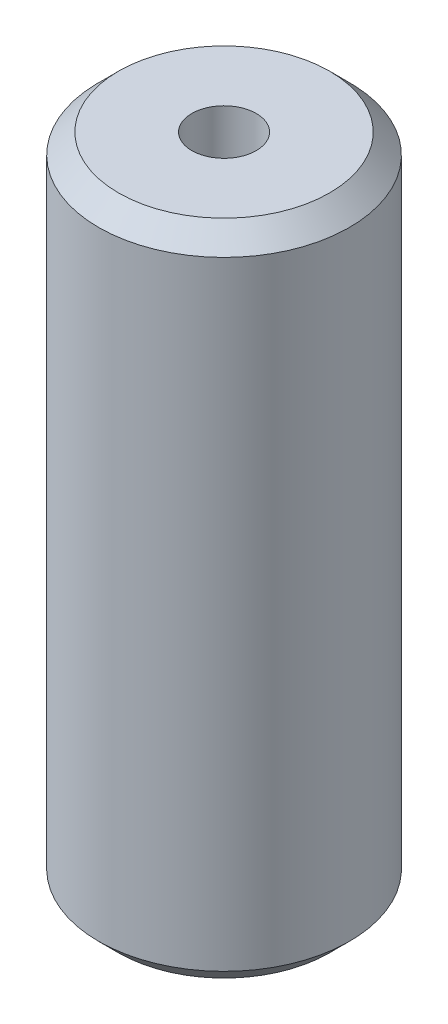
SolidWorks part; units mm, degrees
ref_plane "Front Plane" through (0, 0, 0) normal (0, 0, 1) x (1, 0, 0)
ref_plane "Top Plane" through (0, 0, 0) normal (0, 1, 0) x (1, 0, 0)
ref_plane "Right Plane" through (0, 0, 0) normal (1, 0, 0) x (0, 0, -1)
sketch "Sketch1" plane through (0, 0, 0) normal (0, 1, 0) x (1, 0, 0)
  circle A0 centre (0, 0) radius 5
  dimension "SHAFT_OD" = 10
extrude "Boss-Extrude1" add sketch "Sketch1" along normal blind 26.2351
sketch "Sketch2" plane through (0, 0, 0) normal (0, 1, 0) x (1, 0, 0)
  circle A0 centre (0, 0) radius 1.2842
  dimension "BORE_D" = 2.5683
extrude "Cut-Extrude1" cut sketch "Sketch2" along normal through all
chamfer "Chamfer1" distance 0.7937 angle 45 2 edges at (0, 26.2351, 5) (0, 0, 5)
